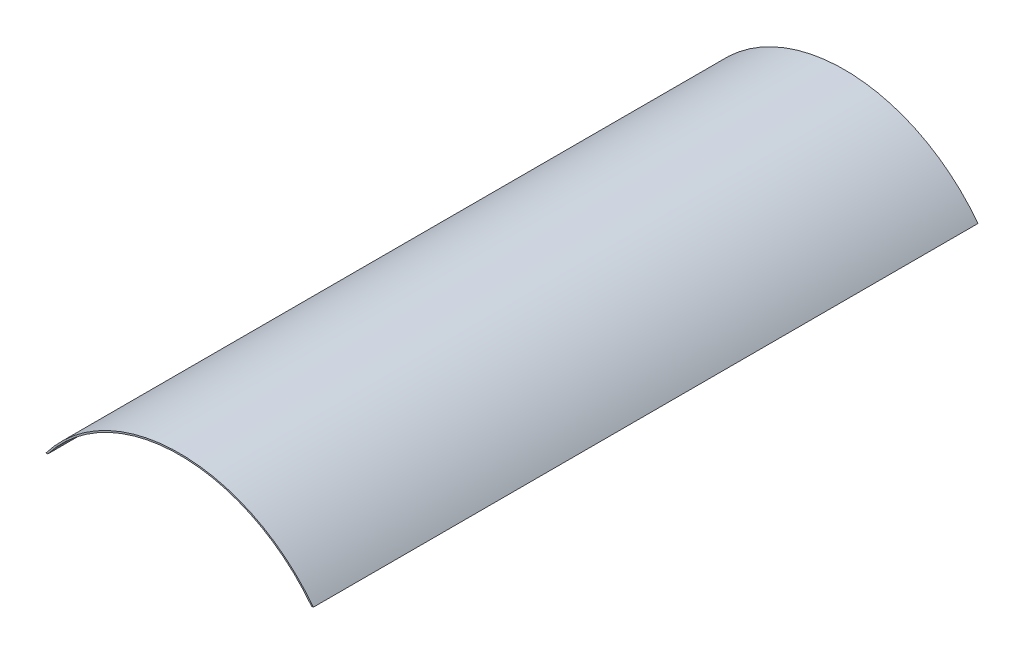
SolidWorks part; units mm, degrees
ref_plane "Спереди" through (0, 0, 0) normal (0, 0, 1) x (1, 0, 0)
ref_plane "Сверху" through (0, 0, 0) normal (0, 1, 0) x (1, 0, 0)
ref_plane "Справа" through (0, 0, 0) normal (1, 0, 0) x (0, 0, -1)
sketch "Эскиз1" plane through (0, 0, 0) normal (0, 0, 1) x (1, 0, 0)
  line L0 (-35.7, 0) -> (-36.2, 0)
  line L1 (36.2, 0) -> (35.7, 0)
  arc A0 (-35.7, 0) -> (35.7, 0) centre (0, -27.3954) cw
  arc A1 (-36.2, 0) -> (36.2, 0) centre (0, -27.3954) cw
  dimension "D1" = 71.4
  dimension "D3" = 45
  dimension "D2" = 0.5
extrude "Бобышка-Вытянуть1" add sketch "Эскиз1" along normal blind 180
